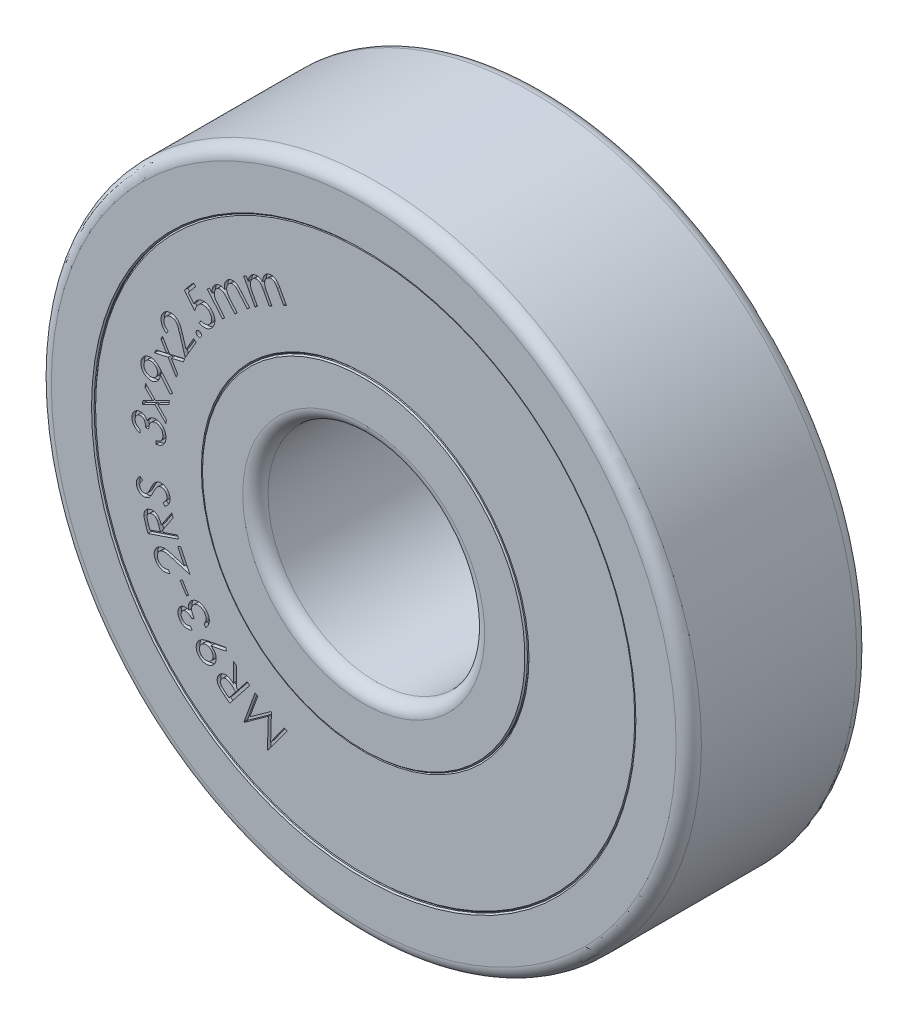
SolidWorks part; units mm, degrees
material "AISI 316 Annealed Stainless Steel Bar (SS)"
ref_plane "Front" through (0, 0, 0) normal (0, 0, 1) x (1, 0, 0)
ref_plane "Top" through (0, 0, 0) normal (0, 1, 0) x (1, 0, 0)
ref_plane "Right" through (0, 0, 0) normal (1, 0, 0) x (0, 0, -1)
sketch "LAYOUT R" plane through (0, 0, 0) normal (1, 0, 0) x (0, 0, -1)
  line L0 (-1.25, 1.5) -> (1.25, 1.5)
  line L1 (1.25, -4.5) -> (-1.25, -4.5) construction
  line L2 (1.25, -4.5) -> (1.25, 4.5) construction
  line L3 (1.25, 4.5) -> (-1.25, 4.5)
  line L4 (-1.25, -4.5) -> (-1.25, 4.5) construction
  line L5 (1.25, -4.5) -> (-1.25, 4.5) construction
  line L6 (1.25, 4.5) -> (-1.25, -4.5) construction
  line L7 (-1.25, 2.25) -> (1.25, 2.25)
  line L8 (-1.25, 3.75) -> (1.25, 3.75)
  line L11 (-17.5, 0) -> (17.5, 0) construction
  line L12 (-1.25, 4.5) -> (-1.25, 3.75)
  line L13 (1.25, 4.5) -> (1.25, 3.75)
  line L14 (-1.25, 3.75) -> (-1.25, 2.25)
  line L15 (1.25, 3.75) -> (1.25, 2.25)
  line L16 (-1.25, 2.25) -> (-1.25, 1.5)
  line L17 (1.25, 2.25) -> (1.25, 1.5)
  line L18 (-1.23, 3.75) -> (-1.23, 2.25)
  line L19 (1.23, 3.75) -> (1.23, 2.25)
  point P0 (0, 0)
  point P15 (0, 0)
  dimension "D1" = 2.5
  dimension "D2" = 9
  dimension "D3" = 1.5
  dimension "D6" = 0.02
  dimension "D7" = 0.02
  dimension "D4" = 2.25
  dimension "D5" = 3.75
sketch "Sketch R, INNER BODY" plane through (0, 0, 0) normal (1, 0, 0) x (0, 0, -1)
  line L0 (-1.25, 1.5) -> (1.25, 1.5) construction
  line L2 (-1.25, 2.25) -> (1.25, 2.25) construction
  line L4 (-1.25, 1.5) -> (1.25, 1.5)
  line L6 (-1.25, 2.25) -> (1.25, 2.25)
  line L8 (1.25, 2.25) -> (1.25, 1.5) construction
  line L9 (-1.25, 2.25) -> (-1.25, 1.5) construction
  line L10 (1.25, 2.25) -> (1.25, 1.5)
  line L11 (-1.25, 2.25) -> (-1.25, 1.5)
  line L12 (-17.5, 0) -> (17.5, 0) construction
  line L13 (-17.5, 0) -> (17.5, 0) construction
sketch "Sketch R, OUTER BODY" plane through (0, 0, 0) normal (1, 0, 0) x (0, 0, -1)
  line L2 (-1.25, 3.75) -> (1.25, 3.75) construction
  line L3 (1.25, 4.5) -> (-1.25, 4.5) construction
  line L6 (-1.25, 3.75) -> (1.25, 3.75)
  line L7 (1.25, 4.5) -> (-1.25, 4.5)
  line L8 (-17.5, 0) -> (17.5, 0) construction
  line L9 (-17.5, 0) -> (17.5, 0) construction
  line L10 (1.25, 4.5) -> (1.25, 3.75) construction
  line L11 (-1.25, 4.5) -> (-1.25, 3.75) construction
  line L12 (1.25, 4.5) -> (1.25, 3.75)
  line L13 (-1.25, 4.5) -> (-1.25, 3.75)
sketch "Sketch R, SEAL FACES" plane through (0, 0, 0) normal (1, 0, 0) x (0, 0, -1)
  line L0 (-17.5, 0) -> (17.5, 0) construction
  line L1 (-17.5, 0) -> (17.5, 0) construction
  line L3 (-1.25, 2.25) -> (1.25, 2.25) construction
  line L5 (-1.25, 3.75) -> (1.25, 3.75) construction
  line L7 (-1.23, 2.25) -> (1.23, 2.25)
  line L9 (-1.23, 3.75) -> (1.23, 3.75)
  line L10 (1.23, 3.75) -> (1.23, 2.25) construction
  line L11 (-1.23, 3.75) -> (-1.23, 2.25) construction
  line L12 (1.23, 3.75) -> (1.23, 2.25)
  line L13 (-1.23, 3.75) -> (-1.23, 2.25)
revolve "Revolve INNER BODY" add sketch "Sketch R, INNER BODY" angle 360 about L13
fillet "Fillet INNER BODY" radius 0.175 2 edges at (1.5, 0, 1.25) (1.5, 0, -1.25)
chamfer "Chamfer INNER BODY" distance 0.018 angle 45 2 edges at (2.25, 0, -1.25) (2.25, 0, 1.25)
revolve "Revolve OUTER BODY" add sketch "Sketch R, OUTER BODY" angle 360 about L9
fillet "Fillet OUTER BODY" radius 0.175 2 edges at (4.5, 0, -1.25) (4.5, 0, 1.25)
chamfer "Chamfer OUTER BODY" distance 0.018 angle 45 2 edges at (3.75, 0, 1.25) (3.75, 0, -1.25)
revolve "Revolve SEALS" add sketch "Sketch R, SEAL FACES" angle 360 about L1
chamfer "Chamfer SEALS" distance 0.018 angle 45 4 edges at (2.25, 0, -1.23) (3.75, 0, -1.23) (3.75, 0, 1.23) (2.25, 0, 1.23)
sketch "Sketch TEXT RADIUS 1 — MANUALLY ASSIGN TEXT AND FONT SIZE (FROM EQUATIONS)" plane through (0, 0, 1.23) normal (0, 0, 1) x (1, 0, 0)
  circle A0 centre (0, 0) radius 2.775 construction
  text T0 "MR93-2RS  3x9x2.5mm" font "Century Gothic" height 0.45
  dimension "D1" = 5.55
extrude "Cut-Extrude SEAL LABEL 1" cut sketch "Sketch TEXT RADIUS 1 — MANUALLY ASSIGN TEXT AND FONT SIZE (FROM EQUATIONS)" against normal blind 0.05
sketch "Sketch TEXT RADIUS 2 — MANUALLY ASSIGN TEXT AND FONT SIZE (FROM EQUATIONS)" plane through (0, 0, -1.23) normal (0, 0, -1) x (-1, 0, 0)
  circle A0 centre (0, 0) radius 2.775 construction
  text T0 "MR93-2RS  3x9x2.5mm\r\n" font "Century Gothic" height 0.45
  dimension "D1" = 5.55
extrude "Cut-Extrude SEAL LABEL 2" cut sketch "Sketch TEXT RADIUS 2 — MANUALLY ASSIGN TEXT AND FONT SIZE (FROM EQUATIONS)" against normal blind 0.05
equation "\"_i__BORE\"= 3"
equation "\"_i__OUTSIDE_DIAMETER\"= 9"
equation "\"_i__WIDTH\"= 2.5"
equation "\"_i_optional__TEXT_RADIUS_ADJUSTMENT\"= 0"
equation "\"_output__FONT_SIZE_mm\"= \"BODY_SPAN__SEAL__OF_RADIUS\" * \"param__FONT_SIZE_RATIO\"'MANUALLY ASSIGN TO FONT"
equation "\"BODY__HALF_WIDTH\"= \"_i__WIDTH\" / 2"
equation "\"BODY_SPAN___OF_DIAMETER\"= \"_i__OUTSIDE_DIAMETER\" - \"_i__BORE\""
equation "\"BODY_SPAN___OF_RADIUS\"= \"BODY_SPAN___OF_DIAMETER\" / 2"
equation "\"BODY_SPAN__BORE_AND_OD__OF RADIUS\"= ( \"BODY_SPAN___OF_RADIUS\" - \"BODY_SPAN__SEAL__OF_RADIUS\" ) / 2"
equation "\"BODY_SPAN__SEAL__OF_RADIUS\"= \"BODY_SPAN___OF_RADIUS\" * \"param__SEAL_PANEL_SPAN__RATIO_OF_BODY_RADIAN\""
equation "\"BORE__RADIUS\"= \"_i__BORE\" / 2"
equation "\"CORNER_RADII\"= \"_i__WIDTH\" * \"param__CORNER_RADII__ISO_MAX_RATIO_TO_WIDTH\""
equation "\"param__CORNER_RADII__ISO_MAX_RATIO_TO_WIDTH\"= 0.07'WHERE WIDTH IS LESS THAN DIAMETER"
equation "\"param__FONT_SIZE_RATIO\"= 0.3"
equation "\"param__SEAL_FACE_INSET__RATIO_OF_WIDTH\"= .01"
equation "\"param__SEAL_PANEL_SPAN__RATIO_OF_BODY_RADIAN\"= 0.5"
equation "\"param__SIDE_CHAMFERS__RATIO_TO_OD\"= 1 / 500"
equation "\"RING_INNER__OUTSIDE_RADIUS\"= \"BORE__RADIUS\" + \"BODY_SPAN__BORE_AND_OD__OF RADIUS\""
equation "\"RING_OUTER__OUTSIDE_RADIUS\"= ( \"_i__OUTSIDE_DIAMETER\" / 2 ) - \"BODY_SPAN__BORE_AND_OD__OF RADIUS\""
equation "\"SEAL_FACE_INSET\"= \"_i__WIDTH\" * \"param__SEAL_FACE_INSET__RATIO_OF_WIDTH\""
equation "\"SIDE_FACE_AND_SEAL_CHAMFERS\"= \"_i__OUTSIDE_DIAMETER\" * \"param__SIDE_CHAMFERS__RATIO_TO_OD\""
equation "\"TEXT_RADIUS\"= \"_i__BORE\" + ( \"BODY_SPAN___OF_DIAMETER\" / 2 ) - \"_output__FONT_SIZE_mm\" + \"_i_optional__TEXT_RADIUS_ADJUSTMENT\""
equation "\"D1@Chamfer INNER BODY\"=\"SIDE_FACE_AND_SEAL_CHAMFERS\""
equation "\"D1@Chamfer OUTER BODY\"=\"SIDE_FACE_AND_SEAL_CHAMFERS\""
equation "\"D1@Chamfer SEALS\"=\"SIDE_FACE_AND_SEAL_CHAMFERS\""
equation "\"D1@Fillet INNER BODY\"=\"CORNER_RADII\""
equation "\"D1@Fillet OUTER BODY\"=\"CORNER_RADII\""
equation "\"D1@LAYOUT R\"=\"_i__WIDTH\""
equation "\"D1@Sketch TEXT RADIUS 1 — MANUALLY ASSIGN TEXT AND FONT SIZE (FROM EQUATIONS)\" = \"TEXT_RADIUS\""
equation "\"D1@Sketch TEXT RADIUS 2 — MANUALLY ASSIGN TEXT AND FONT SIZE (FROM EQUATIONS)\" = \"TEXT_RADIUS\""
equation "\"D2@LAYOUT R\"=\"_i__OUTSIDE_DIAMETER\""
equation "\"D3@LAYOUT R\"=\"BORE__RADIUS\""
equation "\"D4@LAYOUT R\"=\"RING_INNER__OUTSIDE_RADIUS\""
equation "\"D5@LAYOUT R\"=\"RING_OUTER__OUTSIDE_RADIUS\""
